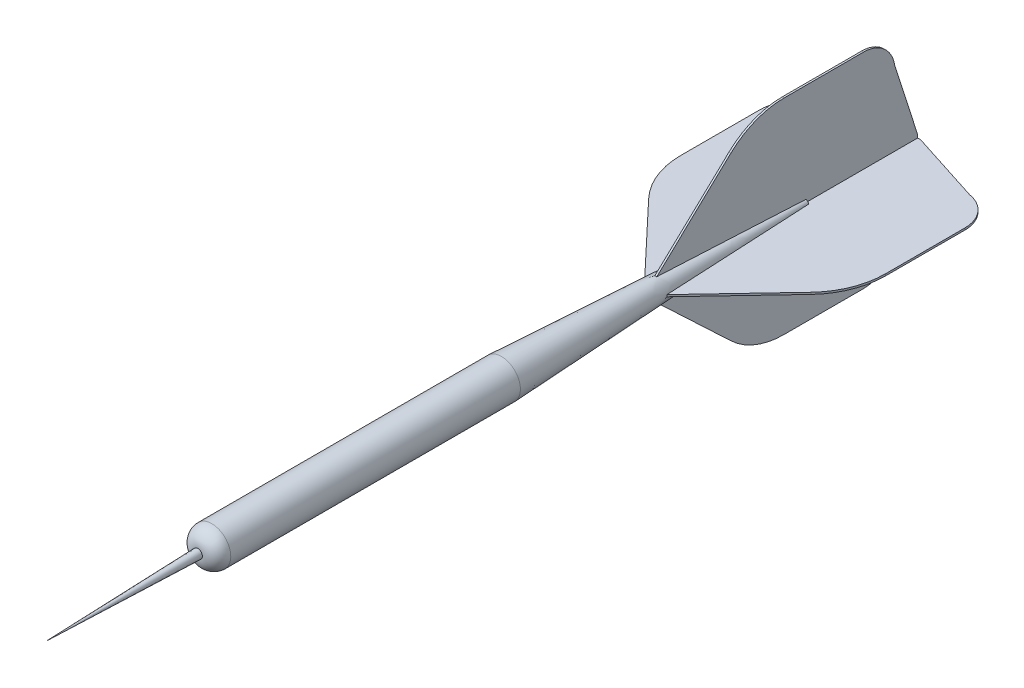
SolidWorks part; units mm, degrees
ref_plane "Front" through (0, 0, 0) normal (0, 0, 1) x (1, 0, 0)
ref_plane "Top" through (0, 0, 0) normal (0, 1, 0) x (1, 0, 0)
ref_plane "Right" through (0, 0, 0) normal (1, 0, 0) x (0, 0, -1)
sketch "Sketch1" plane through (0, 0, 0) normal (1, 0, 0) x (0, 0, -1)
  line L0 (0, 0) -> (-20, 0)
  line L1 (-20, 0) -> (0, 0.6)
  line L2 (1.8439, 2.5) -> (40, 2.5)
  line L3 (40, 2.5) -> (80, 0.5)
  line L4 (80, 0.5) -> (80, 0)
  line L5 (80, 0) -> (0, 0)
  line L6 (-20, 0) -> (-26.2078, 0) construction
  arc A0 (0, 0.6) -> (1.8439, 2.5) centre (1.8439, 0.6553) cw
  point P6 (5.2467, 2.5)
  point P10 (0, 0)
  point P12 (40.0129, 2.5)
  point P13 (40, 2.5)
  point P14 (40, 2.5)
  point P15 (0, 0)
  dimension "D1" = 100
  dimension "D2" = 0.5
  dimension "D3" = 1.2
  dimension "D4" = 5
  dimension "D5" = 20
  dimension "D6" = 40
revolve "Dart" add sketch "Sketch1" angle 360 about L5
sketch "Sketch3" plane through (0, 0, 0) normal (1, 0, 0) x (0, 0, -1)
  line L0 (58.7736, 0) -> (70.105, 10.706)
  line L2 (77.1172, 13.4947) -> (87.5812, 13.4947)
  line L4 (94.7191, 0) -> (58.7736, 0)
  line L5 (91.6743, 10.001) -> (94.7191, 0.5)
  line L6 (94.7191, 0.5) -> (94.7191, 0)
  arc A0 (70.105, 10.706) -> (77.1172, 13.4947) centre (77.1172, 3.2842) cw
  arc A1 (87.5812, 13.4947) -> (91.6743, 10.001) centre (87.5812, 9.3502) cw
extrude "Flight" add sketch "Sketch3" along normal mid plane 0.25
pattern_circular "Flights" count 4 over 360 about axis through (0, 0, -80) along (0, 0, -1) of "Flight"
sketch "Sketch4" plane through (0, 0, 0) normal (0, 0, 1) x (1, 0, 0)
  line L0 (15.5733, 0) -> (0, 0) construction
  line L1 (0, 0) -> (14.4278, 14.4278) construction
  point P3 (14.4278, 14.4278)
  dimension "D1" = 45
sketch "Sketch6" plane through (0, 0, 0) normal (1, 0, 0) x (0, 0, -1)
  line L0 (0, 0) -> (21.0498, 0) construction
ref_plane "45 Degreen Plane" through (0, 0, 0) normal (-0.7071, 0.7071, 0) x (0.7071, 0.7071, 0)
sketch "Pocket Guide" plane through (0, 0, 0) normal (0, 0, 1) x (1, 0, 0)
  line L0 (0, 15) -> (0, 0) construction
  line L1 (0, 0) -> (15, 0) construction
  line L2 (-0.05, 15) -> (0.05, 15)
  line L3 (-0.75, 3.7997) -> (-0.75, 14.3)
  line L4 (0.75, 14.3) -> (0.75, 3.7997)
  line L5 (15, 0.05) -> (15, -0.05)
  line L6 (14.3, -0.75) -> (3.7997, -0.75)
  line L7 (14.3, 0.75) -> (3.7997, 0.75)
  line L8 (-3.7997, 0.75) -> (-14.3, 0.75)
  line L9 (-15, 0.05) -> (-15, -0.05)
  line L10 (-14.3, -0.75) -> (-3.7997, -0.75)
  line L11 (0.75, -3.7997) -> (0.75, -14.3)
  line L12 (0.05, -15) -> (-0.05, -15)
  line L13 (-0.75, -14.3) -> (-0.75, -3.7997)
  arc A0 (-3.3247, -1.0938) -> (-1.0938, -3.3247) centre (0, 0) ccw
  arc A1 (1.0938, -3.3247) -> (3.3247, -1.0938) centre (0, 0) ccw
  arc A2 (3.3247, 1.0938) -> (1.0938, 3.3247) centre (0, 0) ccw
  arc A3 (-1.0938, 3.3247) -> (-3.3247, 1.0938) centre (0, 0) ccw
  arc A4 (-0.05, 15) -> (-0.75, 14.3) centre (-0.05, 14.3) ccw
  arc A5 (0.05, 15) -> (0.75, 14.3) centre (0.05, 14.3) cw
  arc A6 (15, 0.05) -> (14.3, 0.75) centre (14.3, 0.05) ccw
  arc A7 (15, -0.05) -> (14.3, -0.75) centre (14.3, -0.05) cw
  arc A8 (0.75, -14.3) -> (0.05, -15) centre (0.05, -14.3) cw
  arc A9 (-0.05, -15) -> (-0.75, -14.3) centre (-0.05, -14.3) cw
  arc A10 (-15, -0.05) -> (-14.3, -0.75) centre (-14.3, -0.05) ccw
  arc A11 (-14.3, 0.75) -> (-15, 0.05) centre (-14.3, 0.05) ccw
  arc A12 (-0.75, 3.7997) -> (-1.0938, 3.3247) centre (-1.25, 3.7997) cw
  arc A13 (0.75, 3.7997) -> (1.0938, 3.3247) centre (1.25, 3.7997) ccw
  arc A14 (3.7997, 0.75) -> (3.3247, 1.0938) centre (3.7997, 1.25) cw
  arc A15 (3.7997, -0.75) -> (3.3247, -1.0938) centre (3.7997, -1.25) ccw
  arc A16 (0.75, -3.7997) -> (1.0938, -3.3247) centre (1.25, -3.7997) cw
  arc A17 (-0.75, -3.7997) -> (-1.0938, -3.3247) centre (-1.25, -3.7997) ccw
  arc A18 (-3.7997, -0.75) -> (-3.3247, -1.0938) centre (-3.7997, -1.25) cw
  arc A19 (-3.7997, 0.75) -> (-3.3247, 1.0938) centre (-3.7997, 1.25) ccw
  point P19 (0, 0)
  point P22 (0, 0)
  point P23 (0, 0)
  point P24 (-1.307, -14.3675)
  point P30 (15, 0.75)
  point P33 (15, -0.75)
  point P44 (-0.75, 3.4187)
  point P47 (0.75, 3.4187)
  point P50 (3.4187, 0.75)
  point P53 (3.4187, -0.75)
  point P56 (0.75, -3.4187)
  dimension "D1" = 7
  dimension "D4" = 0.7
  dimension "D5" = 0.5
  dimension "D2" = 30
  dimension "D3" = 1.5
sketch "Pin Pocket Guide" plane through (0, 0, 0) normal (0, 0, 1) x (1, 0, 0)
  circle A0 centre (0, 0) radius 1
  dimension "D1" = 2
sketch "Shaft Pocket Guide" plane through (0, 0, 0) normal (0, 0, 1) x (1, 0, 0)
  circle A0 centre (0, 0) radius 3.5
